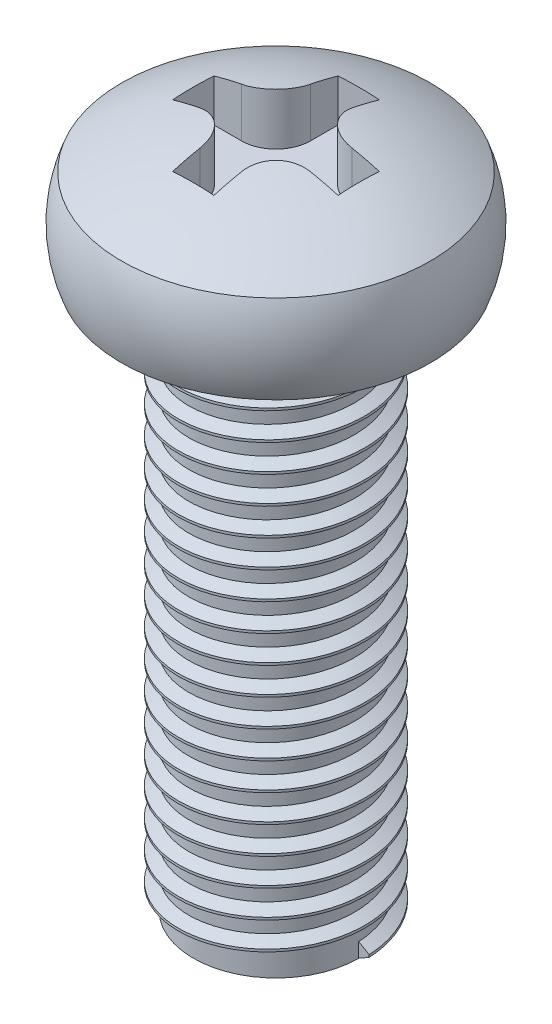
SolidWorks part; units mm, degrees
ref_plane "Front Plane" through (0, 0, 0) normal (0, 0, 1) x (1, 0, 0)
ref_plane "Top Plane" through (0, 0, 0) normal (0, 1, 0) x (1, 0, 0)
ref_plane "Right Plane" through (0, 0, 0) normal (1, 0, 0) x (0, 0, -1)
sketch "Sketch1" plane through (0, 0, 0) normal (0, 0, 1) x (1, 0, 0)
  line L0 (0, 2.4) -> (0, 1.6)
  line L1 (0, 0) -> (2.8, 0)
  line L2 (0, 0) -> (0, 1.6)
  line L3 (0, 1.6) -> (2.8, 1.6)
  line L4 (2.8, 0) -> (2.8, 1.6)
  line L5 (0, 2.4) -> (2.8, 2.4) construction
  arc A0 (2.8, 1.6) -> (0, 2.4) centre (0, -2.9) ccw
  arc A1 (2.8, 1.6) -> (2.8, 0) centre (0.7417, 0.8) cw
  point P9 (2.95, 0.8)
  dimension "D1" = 2.4
  dimension "D2" = 2.8
  dimension "D3" = 1.6
  dimension "D4" = 2.95
revolve "Revolve1" add sketch "Sketch1" angle 360 about L0
ref_plane "Plane1" through (0, 2.4, 0) normal (0, 1, 0) x (1, 0, 0)
sketch "Sketch2" plane through (0, 2.4, 0) normal (0, 1, 0) x (1, 0, 0)
  line L1 (0.375, -1.5) -> (-0.375, -1.5)
  line L2 (0.375, -1.5) -> (0.375, 1.5)
  line L3 (0.375, 1.5) -> (-0.375, 1.5)
  line L4 (-0.375, -1.5) -> (-0.375, 1.5)
  line L5 (0.375, -1.5) -> (-0.375, 1.5) construction
  line L6 (0.375, 1.5) -> (-0.375, -1.5) construction
  line L7 (1.5, -0.375) -> (-1.5, -0.375)
  line L8 (1.5, -0.375) -> (1.5, 0.375)
  line L9 (1.5, 0.375) -> (-1.5, 0.375)
  line L10 (-1.5, -0.375) -> (-1.5, 0.375)
  line L11 (1.5, -0.375) -> (-1.5, 0.375) construction
  line L12 (1.5, 0.375) -> (-1.5, -0.375) construction
  arc A0 (-0.375, 1) -> (-1, 0.375) centre (-1, 1) cw
  arc A1 (-1, -0.375) -> (-0.375, -1) centre (-1, -1) cw
  arc A2 (0.375, -1) -> (1, -0.375) centre (1, -1) cw
  arc A3 (1, 0.375) -> (0.375, 1) centre (1, 1) cw
  point P0 (0, 0)
  point P6 (0, 0)
  dimension "D3" = 0.5
  dimension "D1" = 3
  dimension "D2" = 0.75
extrude "Cut-Extrude1" cut sketch "Sketch2" against normal blind 1 contours L9 L2 L3 L4 | L4 A0 L9 | L10 L7 L4 L9 | L2 L9 L4 L7 | L2 L7 L4 L1 | L8 L9 L2 L7 | L9 A3 L2 | L2 A2 L7 | L7 A1 L4
sketch "Sketch3" plane through (0, 0, 0) normal (0, -1, 0) x (1, 0, 0)
  circle A0 centre (0, 0) radius 1.5
  dimension "D1" = 3
extrude "Boss-Extrude1" add sketch "Sketch3" along normal blind 10
thread "Thread1" pitch 0.35 start angle 0, offset 0, length 10, pitch 0.5, diameter 3
ref_plane "Plane2" through (1.5, 0, 0) normal (0, 0, 1) x (1, 0, 0)
sketch "Thread Profile1" plane through (1.5, 0, 0) normal (0, 0, 1) x (1, 0, 0)
  line L0 (0, 0) -> (0, 0.35) construction
  line L1 (0, 0) -> (0.1894, 0.1094)
  line L2 (0.1894, 0.1094) -> (0.1894, 0.1531)
  line L3 (0.1894, 0.1531) -> (0, 0.2625)
  line L4 (0.1894, 0.1312) -> (0, 0.1312) construction
  line L11 (0, 0) -> (0, 0.2625)
  point P2 (0, 0)
  dimension "Pitch" = 0.35
  dimension "Profile_Angle" = 60
  dimension "Profile_Land" = 0.0437
  dimension "Profile_Height" = 0.1894
